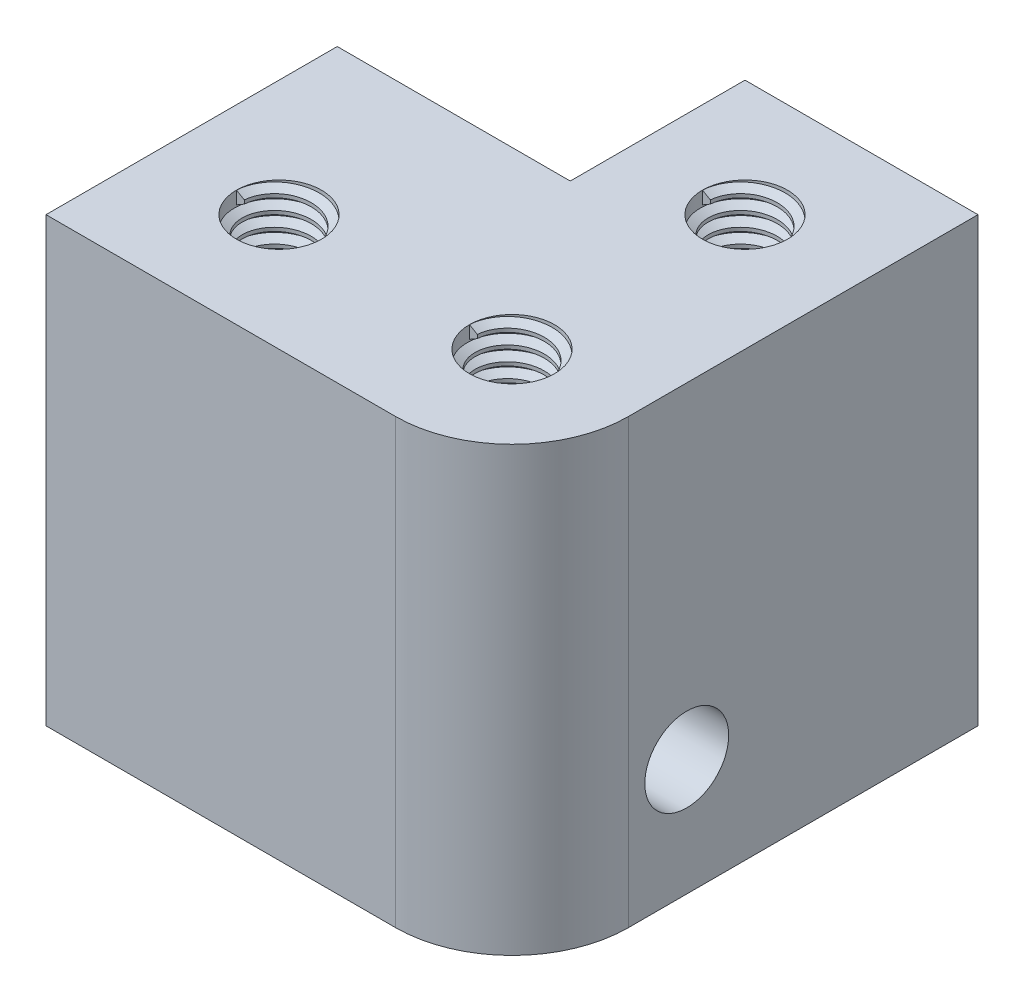
SolidWorks part; units mm, degrees
material "Copper"
ref_plane "Front Plane" through (0, 0, 0) normal (0, 0, 1) x (1, 0, 0)
ref_plane "Top Plane" through (0, 0, 0) normal (0, 1, 0) x (1, 0, 0)
ref_plane "Right Plane" through (0, 0, 0) normal (1, 0, 0) x (0, 0, -1)
sketch "Sketch1" plane through (0, 0, 0) normal (0, 1, 0) x (1, 0, 0)
  line L0 (0, 15.875) -> (12.7, 15.875)
  line L1 (0, 0) -> (19.05, 0)
  line L2 (0, 0) -> (0, 15.875)
  line L3 (12.7, 25.4) -> (25.4, 25.4)
  line L4 (25.4, 6.35) -> (25.4, 25.4)
  line L5 (12.7, 15.875) -> (12.7, 25.4)
  arc A0 (19.05, 0) -> (25.4, 6.35) centre (19.05, 6.35) ccw
  point P7 (25.4, 0)
  point P12 (12.7, 25.4)
  point P15 (12.7, 15.875)
  dimension "D3" = 6.35
  dimension "D1" = 25.4
  dimension "D2" = 25.4
  dimension "D4" = 12.7
  dimension "D5" = 9.525
extrude "Base Extrude" add sketch "Sketch1" along normal blind 24.13
sketch "Sketch2" plane through (25.4, 0, 0) normal (1, 0, 0) x (0, 0, -1)
  line L0 (6.35, 0) -> (25.4, 0) construction
  line L1 (0, 24.13) -> (0, 0) construction
  circle A0 centre (9.525, 6.35) radius 2.286
  dimension "D1" = 4.572
  dimension "D2" = 6.35
  dimension "D3" = 9.525
extrude "Axle Cut" cut sketch "Sketch2" against normal through all
sketch "Sketch3" plane through (0, 24.13, 0) normal (0, 1, 0) x (1, 0, 0)
  line L3 (12.7, 25.4) -> (12.7, 15.875) construction
  line L5 (0, 0) -> (19.05, 0) construction
  circle A0 centre (6.35, 6.35) radius 2.3177
  circle A1 centre (19.05, 6.35) radius 2.3178
  circle A2 centre (19.05, 19.05) radius 2.3178
  dimension "D1" = 4.6355
  dimension "D5" = 6.35
  dimension "D2" = 12.7
  dimension "D3" = 12.7
  dimension "D4" = 6.35
extrude "Mouting Hole Cut" cut sketch "Sketch3" against normal blind 12.7
thread "Front Thread" pitch 0.7937 start angle 0, offset 0, length 12.7, pitch 0.7937, diameter 4.6355
ref_plane "Plane1" through (4.0322, 24.13, -6.35) normal (0, 0, 1) x (-1, 0, 0)
sketch "Thread Profile1" plane through (4.0322, 24.13, -6.35) normal (0, 0, 1) x (-1, 0, 0)
  line L0 (0, 0) -> (0, 0.7937) construction
  line L11 (0, 0) -> (0, 0.6945)
  line L12 (0, 0.6945) -> (-0.4296, 0.4465)
  line L13 (-0.4296, 0.4465) -> (-0.4296, 0.248)
  line L15 (-0.4296, 0.248) -> (0, 0)
  line L17 (-0.4296, 0.3473) -> (0, 0.3473) construction
  point P2 (0, 0)
  dimension "Pitch" = 0.7937
  dimension "Profile_Angle" = 60
  dimension "Profile_Land" = 0.1984
  dimension "Profile_Height" = 0.4296
thread "Middle Thread" pitch 0.7937 profile "Thread Profile2" start angle 0, offset 0, length 12.7, pitch 0.7937, diameter 4.6355
ref_plane "Plane2" through (16.7322, 24.13, -6.35) normal (0, 0, 1) x (-1, 0, 0)
sketch "Thread Profile2" plane through (16.7322, 24.13, -6.35) normal (0, 0, 1) x (-1, 0, 0)
  line L0 (0, 0) -> (0, 0.7937) construction
  line L11 (0, 0) -> (0, 0.6945)
  line L12 (0, 0.6945) -> (-0.4296, 0.4465)
  line L13 (-0.4296, 0.4465) -> (-0.4296, 0.248)
  line L15 (-0.4296, 0.248) -> (0, 0)
  line L17 (-0.4296, 0.3473) -> (0, 0.3473) construction
  point P2 (0, 0)
  dimension "Pitch" = 0.7937
  dimension "Profile_Angle" = 60
  dimension "Profile_Land" = 0.1984
  dimension "Profile_Height" = 0.4296
thread "Side Thread" pitch 0.7937 profile "Thread Profile3" start angle 0, offset 0, length 12.7, pitch 0.7937, diameter 4.6355
ref_plane "Plane3" through (16.7322, 24.13, -19.05) normal (0, 0, 1) x (-1, 0, 0)
sketch "Thread Profile3" plane through (16.7322, 24.13, -19.05) normal (0, 0, 1) x (-1, 0, 0)
  line L0 (0, 0) -> (0, 0.7937) construction
  line L11 (0, 0) -> (0, 0.6945)
  line L12 (0, 0.6945) -> (-0.4296, 0.4465)
  line L13 (-0.4296, 0.4465) -> (-0.4296, 0.248)
  line L15 (-0.4296, 0.248) -> (0, 0)
  line L17 (-0.4296, 0.3473) -> (0, 0.3473) construction
  point P2 (0, 0)
  dimension "Pitch" = 0.7937
  dimension "Profile_Angle" = 60
  dimension "Profile_Land" = 0.1984
  dimension "Profile_Height" = 0.4296
